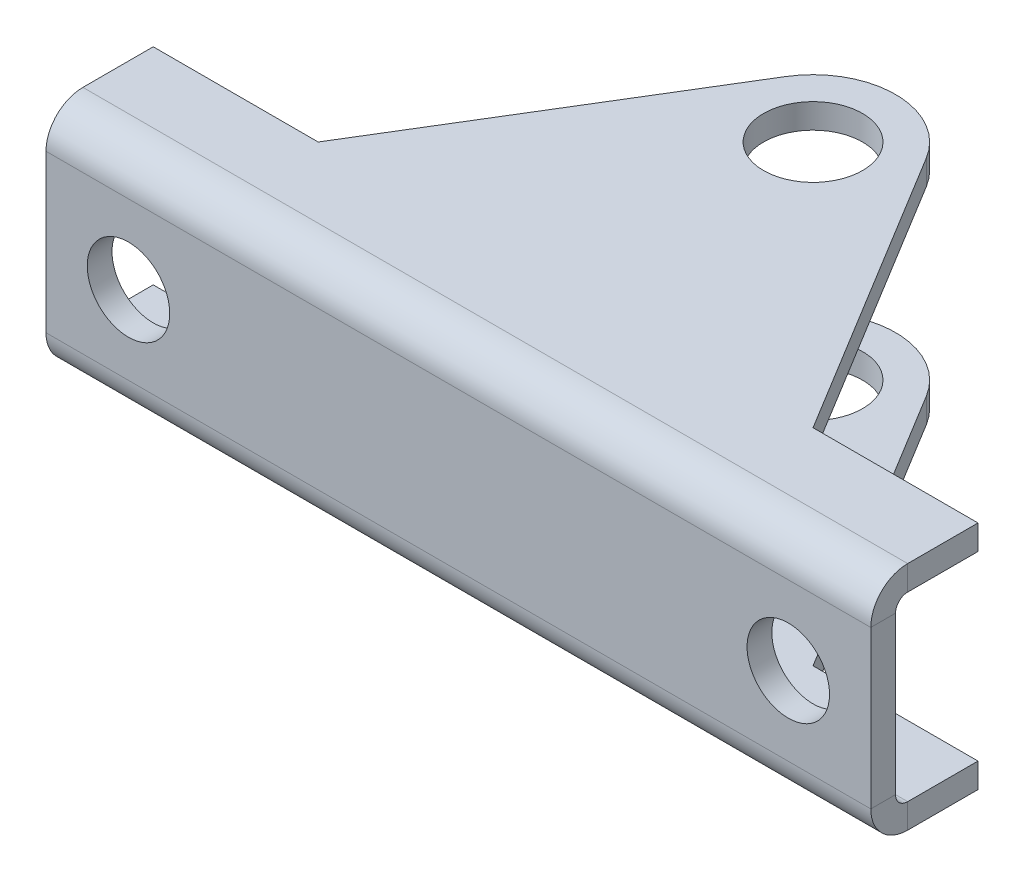
SolidWorks part; units mm, degrees
note: The reader was unsure of these and kept them because the rebuilt part matched: flange length of "Edge-Flange1".
ref_plane "Front Plane" through (0, 0, 0) normal (0, 0, 1) x (1, 0, 0)
ref_plane "Top Plane" through (0, 0, 0) normal (0, 1, 0) x (1, 0, 0)
ref_plane "Right Plane" through (0, 0, 0) normal (1, 0, 0) x (0, 0, -1)
sketch "Sketch1" plane through (0, 0, 0) normal (0, 0, 1) x (1, 0, 0)
  line L1 (-25, 5.5) -> (25, 5.5)
  line L2 (-25, 5.5) -> (-25, -5.5)
  line L3 (-25, -5.5) -> (25, -5.5)
  line L4 (25, 5.5) -> (25, -5.5)
  line L5 (-25, 5.5) -> (25, -5.5) construction
  line L6 (-25, -5.5) -> (25, 5.5) construction
  circle A0 centre (-20, 0) radius 2.5
  circle A1 centre (20, 0) radius 2.5
  point P0 (0, 0)
  dimension "D3" = 5
  dimension "D1" = 50
  dimension "D2" = 11
  dimension "D4" = 40
  dimension "D5" = 20
sheet metal parameters "Sheet-Metal1" thickness 1.5 parameters "D1"=0.7366
base flange "Base-Flange1" sketch "Sketch1" thickness 1.5 reverse thickness direction no parameters "D1"=0.7366
edge flange "Edge-Flange1" sketch "Sketch8" flange profiles "Sketch8", "Sketch9" flange angle 90 flange length 5 flange position material outside bend radius 0.7366 thickness 1.5 relief rectangular parameters "D6"=10, "D8"=1
sketch "Sketch8" plane through (0, 5.5, -1.5) normal (0, -1, 0) x (-1, 0, 0)
  line L1 (25, 0) -> (-25, 0) construction
  line L2 (-25, 0) -> (-25, 5)
  line L3 (-25, 5) -> (25, 5)
  line L4 (25, 5) -> (25, 0)
  line L5 (25, 0) -> (-25, 0)
sketch "Sketch9" plane through (0, -5.5, -1.5) normal (0, 1, 0) x (1, 0, 0)
  line L0 (25, 0) -> (-25, 0) construction
  line L1 (25, 0) -> (-25, 0)
  line L2 (25, 0) -> (25, 5)
  line L3 (25, 5) -> (-25, 5)
  line L4 (-25, 5) -> (-25, 0)
bend "EdgeBend1" bend radius 0.7366 bend angle 90 parameters "D5"=1
bend "EdgeBend2" bend radius 0.7366 bend angle 90 parameters "D5"=2
sketch "Sketch10" plane through (0, 7, 0) normal (0, 1, 0) x (1, 0, 0)
  line L0 (-15, 6.5) -> (-4.2693, 24.1026)
  line L1 (-25, 6.5) -> (25, 6.5) construction
  line L2 (15, 6.5) -> (4.2693, 24.1026)
  line L3 (-25, 2.2366) -> (-25, 6.5) construction
  line L4 (25, 6.5) -> (25, 2.2366) construction
  line L5 (-15, 6.5) -> (15, 6.5)
  arc A0 (-4.2693, 24.1026) -> (4.2693, 24.1026) centre (0, 21.5) cw
  circle A1 centre (0, 21.5) radius 3
  dimension "D3" = 5
  dimension "D5" = 6
  dimension "D1" = 10
  dimension "D2" = 10
  dimension "D4" = 15
base flange "Tab2" sketch "Sketch10" thickness 1.5 reverse thickness direction no parameters "D1"=0.7366
mirror "Mirror1" about plane through (0, 0, 0) normal (0, 1, 0) of "Tab2"
flat pattern "Flat-Pattern1" [suppressed]
sketch "Bend-Lines1" plane through (0, 0, 0) normal (0, 1, 0) x (1, 0, 0)
sketch3d "Bounding-Box1" [suppressed]
  line L0 (25, -10, 0) -> (-25, -10, 0) construction
  line L1 (25, 10, 0) -> (-25, 10, 0) construction
  line L2 (25, -10, 0) -> (25, 10, 0) construction
  line L3 (-25, -10, 0) -> (-25, 10, 0) construction
bend of the flat pattern "Flatten-<EdgeBend1>1"
bend of the flat pattern "Flatten-<EdgeBend2>1"
